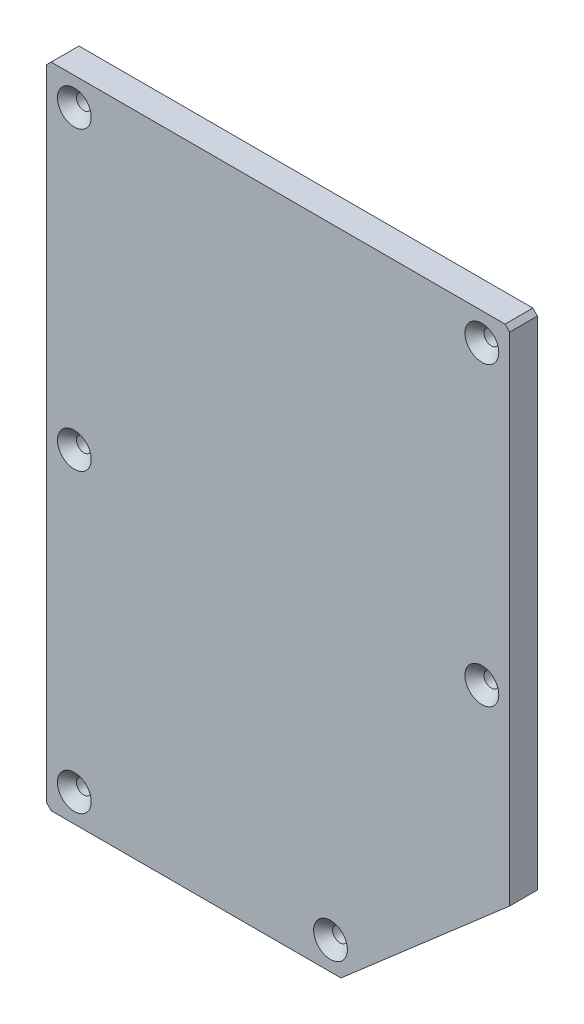
SolidWorks part; units mm, degrees
ref_plane "Front Plane" through (0, 0, 0) normal (0, 0, 1) x (1, 0, 0)
ref_plane "Top Plane" through (0, 0, 0) normal (0, 1, 0) x (1, 0, 0)
ref_plane "Right Plane" through (0, 0, 0) normal (1, 0, 0) x (0, 0, -1)
sketch "Sketch1" plane through (0, 0, 0) normal (0, 0, 1) x (1, 0, 0)
  line L56 (60, -64.7277) -> (60, 42.5997)
  line L57 (60, 42.5997) -> (59, 43.5997)
  line L58 (59, 43.5997) -> (-39, 43.5997)
  line L59 (-39, 43.5997) -> (-40, 42.5997)
  line L60 (-40, 42.5997) -> (-40, -95.4003)
  line L61 (-40, -95.4003) -> (-39, -96.4003)
  line L62 (-39, -96.4003) -> (23.5648, -96.4003)
  line L63 (23.5648, -96.4003) -> (60, -64.7277)
  line L776 (60, -64.7277) -> (60, 42.5997)
  line L777 (60, 42.5997) -> (59, 43.5997)
  line L778 (59, 43.5997) -> (-39, 43.5997)
  line L779 (-39, 43.5997) -> (-40, 42.5997)
  line L780 (-40, 42.5997) -> (-40, -95.4003)
  line L781 (-40, -95.4003) -> (-39, -96.4003)
  line L782 (-39, -96.4003) -> (23.5648, -96.4003)
  line L783 (23.5648, -96.4003) -> (60, -64.7277)
  dimension "D1" = 0
extrude "Boss-Extrude1" add sketch "Sketch1" along normal blind 6
hole_wizard "CSK for M3 Countersunk Flat Head Screw1" positions "3DSketch1" profile "Sketch4" countersink size "M3" standard "ISO" end condition up to next
sketch3d "3DSketch1"
  point P0 (-34, 37.5997, 6)
  point P2 (54, 37.5997, 6)
  point P4 (54, -26.4003, 6)
  point P18 (21.3215, -90.4003, 6)
  point P20 (-34, -90.4003, 6)
  point P22 (-34, -26.4003, 6)
sketch "Sketch4" plane through (-34, 37.5997, 6) normal (1, 0, 0) x (0, -1, 0)
  line L0 (0, 0) -> (0, 6)
  line L1 (0, 6) -> (1.6, 6)
  line L2 (1.6, 6) -> (1.6, 2.05)
  line L3 (1.6, 2.05) -> (3.65, 0)
  line L5 (3.65, 0) -> (0, 0)
  line L6 (-1.6, 2.05) -> (-3.65, 0) construction
  line L11 (0, -6.35) -> (0, 107.95) construction
  dimension "Thru Hole Dia." = 3.2
  dimension "Thru Hole Depth" = 6
  dimension "Near C'Sink Dia." = 7.3
  dimension "Near C'Sink Angle" = 90
